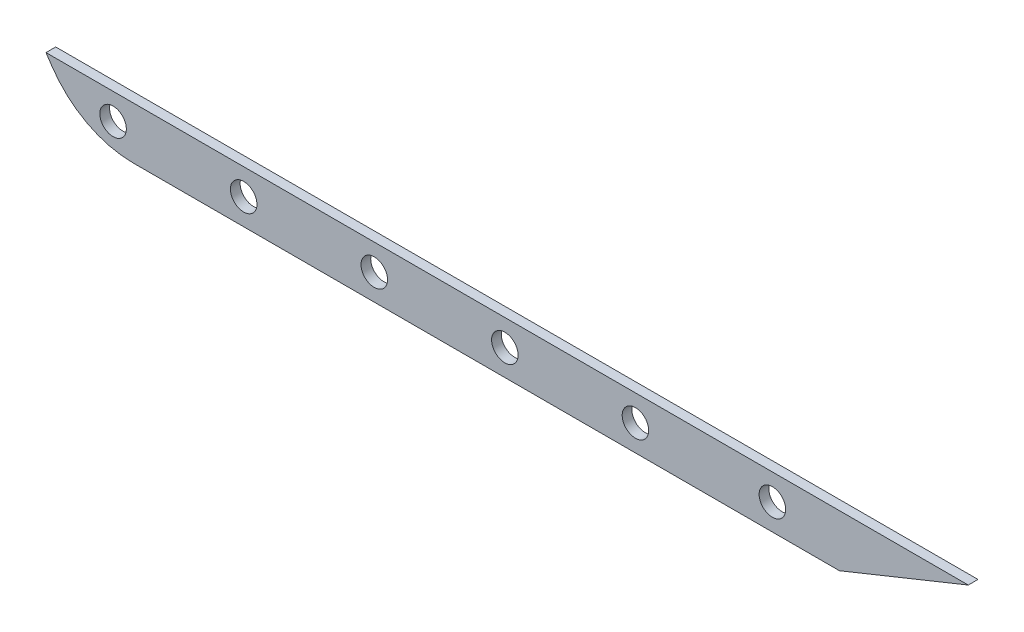
SolidWorks part; units mm, degrees
material "5052-H32"
ref_plane "Front Plane" through (0, 0, 0) normal (0, 0, 1) x (1, 0, 0)
ref_plane "Top Plane" through (0, 0, 0) normal (0, 1, 0) x (1, 0, 0)
ref_plane "Right Plane" through (0, 0, 0) normal (1, 0, 0) x (0, 0, -1)
sketch "Sketch1" plane through (0, 0, 0) normal (0, 0, 1) x (1, 0, 0)
  line L1 (428.1206, 33.3333) -> (428.1206, 28.5708)
  line L3 (428.1206, 28.5708) -> (0, 28.5708)
  line L4 (0, 28.5708) -> (-98.8794, 3.851)
  line L6 (-98.8794, 3.851) -> (-31.8794, -96.649)
  line L7 (428.1206, 28.5708) -> (403.1206, -71.149)
  line L9 (403.1206, -71.149) -> (366, -96.649)
  line L10 (-31.8794, -96.649) -> (366, -96.649)
  circle A0 centre (-16, -83.899) radius 6.5
  circle A1 centre (48, -83.899) radius 6.5
  circle A2 centre (112, -83.899) radius 6.5
  circle A3 centre (176, -83.899) radius 6.5
  circle A4 centre (240, -83.899) radius 6.5
  circle A5 centre (307.1206, -83.899) radius 6.5
  point P0 (-48.8794, -71.149)
  point P2 (-31.8794, -96.649)
  point P8 (48, -83.899)
  point P9 (403.1206, -71.149)
  dimension "D2" = 64
  dimension "D4" = 64
  dimension "D1" = 25.5
  dimension "D3" = 75
  dimension "D5" = 25
  dimension "D6" = 96
  dimension "D7" = 527
  dimension "D9" = 64
  dimension "D10" = 64
  dimension "D11" = 64
  dimension "D12" = 123.69
  dimension "D13" = 12.75
extrude "Boss-Extrude1" add sketch "Sketch1" along normal blind 4.7625 contours L3 L4 L6 L10 L9 L7
extrude "Cut-Extrude1" cut sketch "Sketch1<4>" along normal through all contours A0 | A1 | A2 | A3 | A4 | A5 region at (-16, -83.899, 0)
sketch "Sketch1<4>" plane through (0, 0, 0) normal (0, 0, 1) x (1, 0, 0) same geometry as "Sketch1"
sketch "Sketch2" plane through (0, 0, 0) normal (0, 0, -1) x (-1, 0, 0)
  circle A0 centre (-275.1206, -83.899) radius 6.5
  circle A2 centre (-233.5603, -132.5687) radius 6.5
  circle A3 centre (-192, -83.899) radius 6.5
  circle A4 centre (-128, -83.899) radius 6.5
  circle A5 centre (-64, -83.899) radius 6.5
  circle A6 centre (0, -83.899) radius 6.5
  dimension "D2" = 0
  dimension "D3" = 64
  dimension "D4" = 64
  dimension "D5" = 64
  dimension "D6" = 64
  dimension "D7" = 64
  dimension "D1" = 32
sketch "Sketch5" plane through (0, 0, 0) normal (0, 0, -1) x (-1, 0, 0)
  line L0 (48.8794, -71.149) -> (-14.2353, -96.649)
  line L1 (31.8794, -96.649) -> (-366, -96.649) construction
  line L2 (-14.2353, -96.649) -> (31.8794, -96.649)
  line L3 (31.8794, -96.649) -> (48.8794, -71.149)
  line L6 (-366, -96.649) -> (-403.1206, -71.149)
  line L7 (-403.1206, -71.149) -> (-352, -71.149)
  line L9 (-352, -71.149) -> (-326.5, -96.649)
  line L11 (-366, -96.649) -> (-326.5, -96.649)
  dimension "D1" = 22
  dimension "D2" = 45
sketch "Sketch6" plane through (0, 0, 4.7625) normal (0, 0, 1) x (1, 0, 0)
  line L0 (-48.8794, -71.149) -> (14.2353, -96.649)
  line L1 (-31.8794, -96.649) -> (366, -96.649) construction
  line L2 (14.2353, -96.649) -> (-31.8794, -96.649)
  line L3 (-31.8794, -96.649) -> (-48.8794, -71.149)
  dimension "D1" = 158
sketch "Sketch7" plane through (0, 0, 4.7625) normal (0, 0, 1) x (1, 0, 0)
  line L0 (-48.8794, -71.149) -> (403.1206, -71.149)
  line L1 (-48.8794, -71.149) -> (-98.8794, 3.851)
  line L2 (-98.8794, 3.851) -> (0, 28.5708)
  line L3 (0, 28.5708) -> (428.1206, 28.5708)
  line L4 (428.1206, 28.5708) -> (403.1206, -71.149)
sketch "Sketch8" plane through (0, 0, 4.7625) normal (0, 0, 1) x (1, 0, 0)
  line L0 (-48.8794, -71.149) -> (403.1206, -71.149)
  line L1 (-48.8794, -71.149) -> (-98.8794, 3.851)
  line L2 (-98.8794, 3.851) -> (0, 28.5708)
  line L3 (0, 28.5708) -> (428.1206, 28.5708)
  line L4 (428.1206, 28.5708) -> (403.1206, -71.149)
extrude "Cut-Extrude5" cut sketch "Sketch8" against normal blind 10
fillet "Fillet1" radius 48 1 edges at (-31.8794, -96.649, 2.3813)
sketch "Sketch9" plane through (0, 0, 4.7625) normal (0, 0, 1) x (1, 0, 0)
  line L0 (403.1206, -71.149) -> (340.0059, -96.649)
  line L1 (-31.8794, -96.649) -> (366, -96.649) construction
  line L2 (403.1206, -71.149) -> (366, -96.649)
  line L3 (366, -96.649) -> (340.0059, -96.649)
  dimension "D1" = 22
extrude "Cut-Extrude6" cut sketch "Sketch9" against normal blind 10
